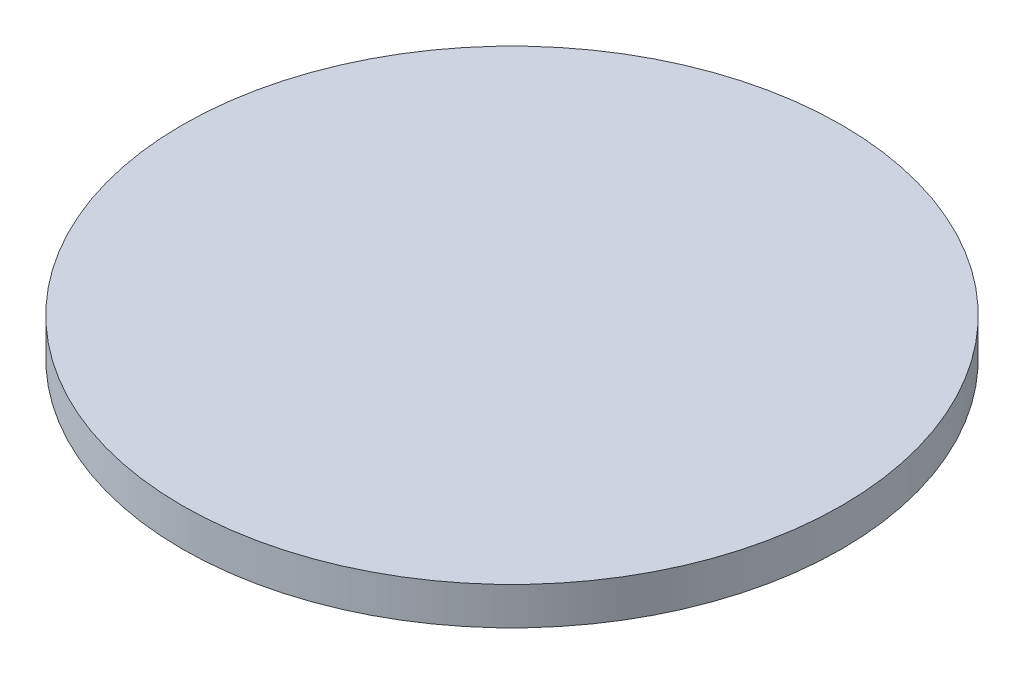
SolidWorks part; units mm, degrees
material "1060 Alloy"
ref_plane "Front Plane" through (0, 0, 0) normal (0, 0, 1) x (1, 0, 0)
ref_plane "Top Plane" through (0, 0, 0) normal (0, 1, 0) x (1, 0, 0)
ref_plane "Right Plane" through (0, 0, 0) normal (1, 0, 0) x (0, 0, -1)
sketch "Sketch1" plane through (0, 0, 0) normal (0, 1, 0) x (1, 0, 0)
  circle A0 centre (0, 0) radius 17.53
  dimension "D1" = 35.06
extrude "Boss-Extrude1" add sketch "Sketch1" along normal blind 1
sketch "Sketch2" plane through (0, 0, 0) normal (0, -1, 0) x (1, 0, 0)
  circle A0 centre (0, 0) radius 17.53
  circle A1 centre (0, 0) radius 16.53
  circle A2 centre (0, 0) radius 17.53 construction
  dimension "D1" = 0
  dimension "D2" = 33.06
extrude "Boss-Extrude2" add sketch "Sketch2" along normal blind 1
thread "Thread1" pitch 0.25 method cut profile "Thread Profile1" start angle 0, offset 0, length 1, pitch 0.25, diameter 33.06
ref_plane "Plane1" through (16.53, -1, 0) normal (0, 0, 1) x (1, 0, 0)
sketch "Thread Profile1" plane through (16.53, -1, 0) normal (0, 0, 1) x (1, 0, 0)
  line L0 (0, 0) -> (0, 0.25) construction
  line L1 (0, 0) -> (0.1353, 0.0781)
  line L2 (0.1353, 0.0781) -> (0.1353, 0.1094)
  line L3 (0.1353, 0.1094) -> (0, 0.1875)
  line L4 (0.1353, 0.0937) -> (0, 0.0937) construction
  line L11 (0, 0) -> (0, 0.1875)
  point P2 (0, 0)
  dimension "Pitch" = 0.25
  dimension "Profile_Angle" = 60
  dimension "Profile_Land" = 0.0312
  dimension "Profile_Height" = 0.1353
sketch "Sketch3" plane through (0, 0, 0) normal (0, -1, 0) x (1, 0, 0)
  circle A0 centre (0, 0) radius 15.03
  dimension "D1" = 30.06
extrude "Boss-Extrude3" add sketch "Sketch3" along normal blind 1
